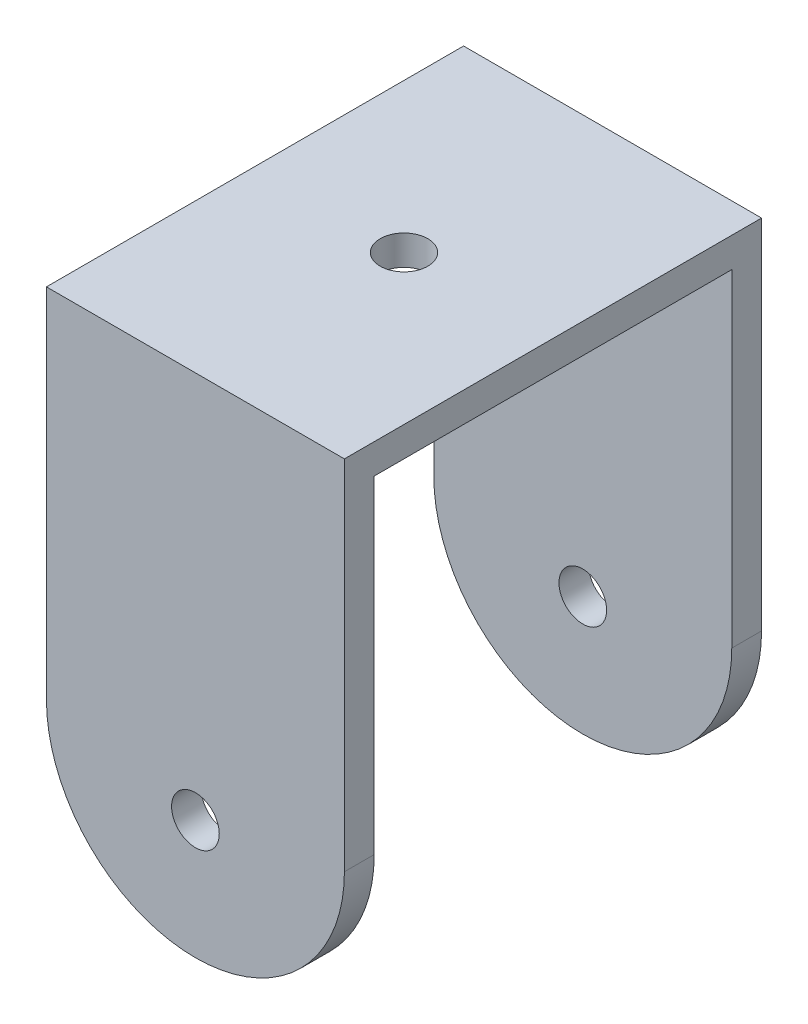
SolidWorks part; units mm, degrees
ref_plane "前视基准面" through (0, 0, 0) normal (0, 0, 1) x (1, 0, 0)
ref_plane "上视基准面" through (0, 0, 0) normal (0, 1, 0) x (1, 0, 0)
ref_plane "右视基准面" through (0, 0, 0) normal (1, 0, 0) x (0, 0, -1)
other "Configuration Table"
sketch "草图1" plane through (0, 0, 0) normal (0, 0, 1) x (1, 0, 0)
  line L1 (-25, 40) -> (25, 40)
  line L2 (-25, 40) -> (-25, -40)
  line L3 (-25, -40) -> (25, -40)
  line L4 (25, 40) -> (25, -40)
  line L5 (-25, 40) -> (25, -40) construction
  line L6 (-25, -40) -> (25, 40) construction
  point P0 (0, 0)
  dimension "D1" = 50
  dimension "D2" = 80
extrude "凸台-拉伸1" add sketch "草图1" along normal blind 5
ref_plane "基准面1" through (0, 0, 65) normal (0, 0, 1) x (1, 0, 0)
sketch "草图2" plane through (0, 0, 65) normal (0, 0, 1) x (1, 0, 0)
  line L4 (25, -40) -> (25, 40)
  line L5 (25, 40) -> (-25, 40)
  line L6 (-25, 40) -> (-25, -40)
  line L7 (-25, -40) -> (25, -40)
  line L8 (25, -40) -> (25, 40)
  line L9 (25, 40) -> (-25, 40)
  line L10 (-25, 40) -> (-25, -40)
  line L11 (-25, -40) -> (25, -40)
  dimension "D1" = 0
extrude "凸台-拉伸2" add sketch "草图2" along normal blind 5 separate body
sketch "草图3" plane through (0, 40, 0) normal (0, 1, 0) x (1, 0, 0)
  line L1 (-25, 0) -> (25, 0)
  line L2 (-25, 0) -> (-25, -70)
  line L3 (-25, -70) -> (25, -70)
  line L4 (25, 0) -> (25, -70)
extrude "凸台-拉伸3" add sketch "草图3" along normal blind 5
sketch "草图4" plane through (0, 0, 70) normal (0, 0, 1) x (1, 0, 0)
  line L0 (0, 56.3532) -> (0, -60.1266) construction
  line L1 (-25, -40) -> (25, -40) construction
  circle A0 centre (0, -20) radius 4
  dimension "D1" = 8
  dimension "D2" = 20
extrude "切除-拉伸1" cut sketch "草图4" against normal through all
sketch "草图5" plane through (0, 45, 0) normal (0, 1, 0) x (1, 0, 0)
  line L0 (-25, -35) -> (44.9291, -35) construction
  line L1 (-25, 0) -> (-25, -70) construction
  line L2 (0, 9.9063) -> (0, -82.4542) construction
  circle A0 centre (0, -35) radius 4
  dimension "D1" = 8
extrude "切除-拉伸2" cut sketch "草图5" against normal through all
fillet "圆角1" radius 25 4 edges at (-25, -40, 2.5) (25, -40, 2.5) (25, -40, 67.5) (-25, -40, 67.5)
